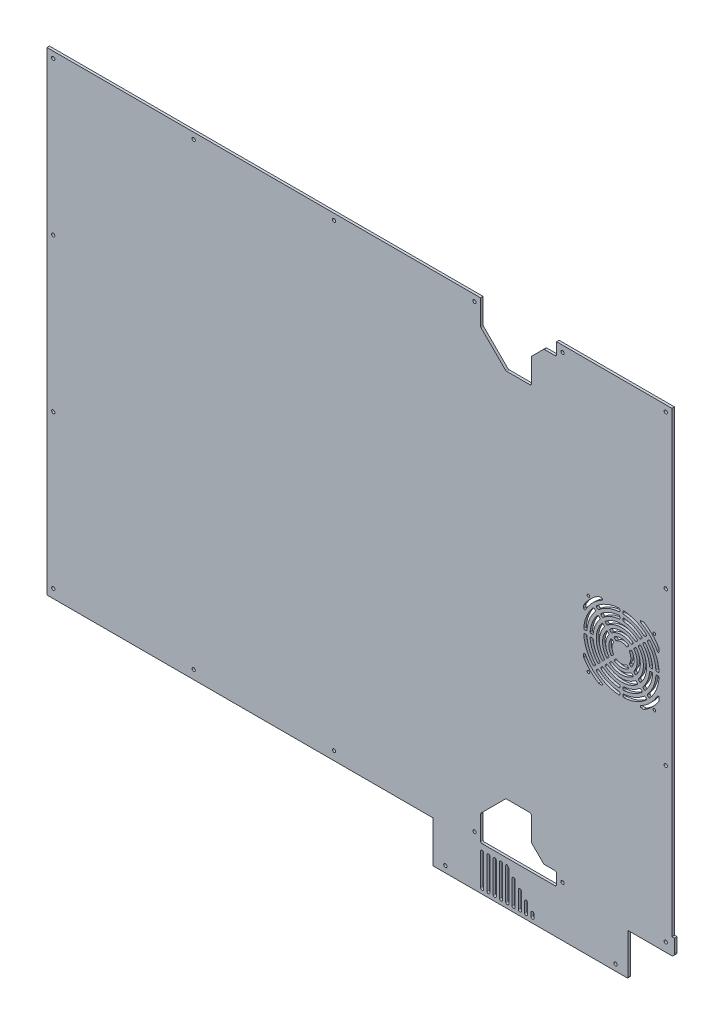
SolidWorks part; units mm, degrees
material "PC Высокая вязкость"
ref_plane "Спереди" through (0, 0, 0) normal (0, 0, 1) x (1, 0, 0)
ref_plane "Сверху" through (0, 0, 0) normal (0, 1, 0) x (1, 0, 0)
ref_plane "Справа" through (0, 0, 0) normal (1, 0, 0) x (0, 0, -1)
sketch "Эскиз1" plane through (0, 0, 0) normal (0, 0, 1) x (1, 0, 0)
  line L68 (0, -4) -> (0, 750)
  line L81 (0, 375) -> (994, 375) construction
  line L82 (0, 0) -> (994, 0) construction
  line L83 (0, 0) -> (0, 750) construction
  line L84 (0, 750) -> (994, 750) construction
  line L85 (994, 0) -> (994, 750) construction
  line L86 (770, 0) -> (770, 750) construction
  line L95 (0, 750) -> (994, 750)
  line L96 (994, 750) -> (994, 22.45)
  line L97 (998, -4) -> (924, -4)
  line L114 (924, -4) -> (924, -70)
  line L115 (924, -70) -> (613.5, -70)
  line L116 (613.5, -70) -> (613.5, -4)
  line L117 (613.5, -4) -> (0, -4)
  line L127 (994, 22.45) -> (998, 22.45)
  line L130 (998, 22.45) -> (998, -4)
  dimension "D3" = 26.45
  dimension "D4" = 4
  dimension "D6" = 613.5
  dimension "D7" = 70
  dimension "D8" = 70
  dimension "D9" = 4
  dimension "D10" = 310.5
  dimension "D12" = 750
  dimension "D17" = 770
  dimension "D18" = 224
extrude "Бобышка-Вытянуть1" add sketch "Эскиз1" along normal blind 4
sketch "Эскиз7" plane through (0, 0, 4) normal (0, 0, 1) x (1, 0, 0)
  line L0 (690, 40) -> (730, 80) construction
  line L1 (730, 80) -> (770, 80) construction
  line L2 (770, 80) -> (770, 40) construction
  line L3 (770, 40) -> (790, 20) construction
  line L4 (790, 20) -> (810, 20) construction
  line L5 (810, 20) -> (810, 0) construction
  line L6 (690, 0) -> (810, 0) construction
  line L7 (690, 0) -> (690, 40) construction
  line L8 (0, 750) -> (0, -4) construction
  line L9 (770, 375) -> (-49230, 375) construction
  line L10 (689.6, -0.4) -> (810.4, -0.4)
  line L11 (810.4, 20.4) -> (810.4, -0.4)
  line L12 (790.1657, 20.4) -> (810.4, 20.4)
  line L13 (770.4, 40.1657) -> (790.1657, 20.4)
  line L14 (770.4, 80.4) -> (770.4, 40.1657)
  line L15 (729.8343, 80.4) -> (770.4, 80.4)
  line L16 (689.6, 40.1657) -> (729.8343, 80.4)
  line L17 (689.6, -0.4) -> (689.6, 40.1657)
  line L18 (0, 0) -> (998, 0) construction
  line L19 (998, -4) -> (998, 22.45) construction
  line L20 (924, -4) -> (998, -4) construction
  line L21 (770, 0) -> (770, 750) construction
  line L22 (994, 750) -> (0, 750) construction
  line L23 (689.6, 750.4) -> (689.6, 709.8343)
  line L24 (689.6, 750.4) -> (810.4, 750.4)
  line L25 (810.4, 729.6) -> (810.4, 750.4)
  line L26 (790.1657, 729.6) -> (810.4, 729.6)
  line L27 (770.4, 709.8343) -> (790.1657, 729.6)
  line L28 (770.4, 669.6) -> (770.4, 709.8343)
  line L29 (729.8343, 669.6) -> (770.4, 669.6)
  line L30 (689.6, 709.8343) -> (729.8343, 669.6)
  point P30 (770, 375)
  dimension "D1" = 40
  dimension "D2" = 120
  dimension "D3" = 40
  dimension "D4" = 20
  dimension "D5" = 40
  dimension "D6" = 20
  dimension "D7" = 40
  dimension "D8" = 40
  dimension "D9" = 20
  dimension "D10" = 20
  dimension "D11" = 770
  dimension "D12" = 4
  dimension "D13" = 0.4
extrude "Вырез-Вытянуть6" cut sketch "Эскиз7" against normal through all
sketch "Эскиз2" plane through (0, 0, 0) normal (0, 0, -1) x (-1, 0, 0)
  line L0 (-984, 739.99) -> (-820, 739.99) construction
  line L1 (-924, -4) -> (-998, -4) construction
  line L2 (-10, 10) -> (-10, 253.33) construction
  line L3 (-10, 10) -> (-233.33, 10) construction
  line L7 (-984, 10) -> (-984, 253.33) construction
  line L10 (-994, 22.45) -> (-994, 750) construction
  line L11 (0, 750) -> (0, -4) construction
  circle A0 centre (-10, 10) radius 2.6
  circle A1 centre (-10, 253.33) radius 2.6
  circle A2 centre (-10, 496.66) radius 2.6
  circle A3 centre (-10, 739.99) radius 2.6
  circle A16 centre (-984, 10) radius 2.6
  circle A17 centre (-984, 253.33) radius 2.6
  circle A18 centre (-984, 496.66) radius 2.6
  circle A19 centre (-984, 739.99) radius 2.6
  circle A261 centre (-820, 739.99) radius 2.6
  circle A262 centre (-820, 10) radius 2.6
  circle A263 centre (-233.33, 10) radius 2.6
  circle A264 centre (-233.33, 739.99) radius 2.6
  circle A265 centre (-456.66, 10) radius 2.6
  circle A266 centre (-456.66, 739.99) radius 2.6
  circle A267 centre (-679.99, 10) radius 2.6
  circle A268 centre (-679.99, 739.99) radius 2.6
  dimension "D1" = 5.2
  dimension "D10" = 5.2
  dimension "D11" = 14
  dimension "D12" = 10
  dimension "D2" = 4
  dimension "D3" = 10
  dimension "D5" = 243.33
  dimension "D9" = 164
  dimension "D14" = 243.33
  dimension "D6" = 223.33
  dimension "D4" = 4
  dimension "D13" = 4
  dimension "D8" = 2
extrude "Вырез-Вытянуть1" cut sketch "Эскиз2" against normal through all
sketch "Эскиз3" plane through (0, 0, 4) normal (0, 0, 1) x (1, 0, 0)
  line L0 (774.5, -62) -> (774.5, -12)
  line L2 (769.5, -12) -> (769.5, -62)
  line L4 (759.5, -12) -> (759.5, -62)
  line L5 (764.5, -62) -> (764.5, -12)
  line L6 (749.5, -12) -> (749.5, -62)
  line L7 (754.5, -62) -> (754.5, -12)
  line L12 (924, -70) -> (924, -4) construction
  line L13 (924, -37) -> (-49076, -37) construction
  line L14 (739.5, -12) -> (739.5, -62)
  line L15 (744.5, -62) -> (744.5, -12)
  line L16 (729.5, -12) -> (729.5, -62)
  line L17 (734.5, -62) -> (734.5, -12)
  line L18 (719.5, -12) -> (719.5, -62)
  line L19 (724.5, -62) -> (724.5, -12)
  line L20 (709.5, -12) -> (709.5, -62)
  line L21 (714.5, -62) -> (714.5, -12)
  line L22 (699.5, -12) -> (699.5, -62)
  line L23 (704.5, -62) -> (704.5, -12)
  line L24 (769.5, -12) -> (759.5, -12) construction
  line L25 (689.5, -12) -> (689.5, -62)
  line L26 (694.5, -62) -> (694.5, -12)
  arc A0 (774.5, -12) -> (769.5, -12) centre (772, -12) ccw
  arc A1 (774.5, -62) -> (769.5, -62) centre (772, -62) cw
  arc A2 (764.5, -62) -> (759.5, -62) centre (762, -62) cw
  arc A3 (764.5, -12) -> (759.5, -12) centre (762, -12) ccw
  arc A4 (754.5, -62) -> (749.5, -62) centre (752, -62) cw
  arc A5 (754.5, -12) -> (749.5, -12) centre (752, -12) ccw
  arc A6 (744.5, -62) -> (739.5, -62) centre (742, -62) cw
  arc A7 (744.5, -12) -> (739.5, -12) centre (742, -12) ccw
  arc A8 (734.5, -62) -> (729.5, -62) centre (732, -62) cw
  arc A9 (734.5, -12) -> (729.5, -12) centre (732, -12) ccw
  arc A10 (724.5, -62) -> (719.5, -62) centre (722, -62) cw
  arc A11 (724.5, -12) -> (719.5, -12) centre (722, -12) ccw
  arc A12 (714.5, -62) -> (709.5, -62) centre (712, -62) cw
  arc A13 (714.5, -12) -> (709.5, -12) centre (712, -12) ccw
  arc A14 (704.5, -62) -> (699.5, -62) centre (702, -62) cw
  arc A15 (704.5, -12) -> (699.5, -12) centre (702, -12) ccw
  arc A16 (694.5, -62) -> (689.5, -62) centre (692, -62) cw
  arc A17 (694.5, -12) -> (689.5, -12) centre (692, -12) ccw
  point P6 (774.5, -37)
  point P17 (924, -37)
  dimension "D4" = 50
  dimension "D2" = 149.5
  dimension "D3" = 5
  dimension "D5" = 10
  dimension "D1" = 9
extrude "Вырез-Вытянуть2" cut sketch "Эскиз3" against normal through all
sketch "Эскиз5" plane through (0, 0, 4) normal (0, 0, 1) x (1, 0, 0)
  line L0 (730, -8) -> (784.5, -8)
  line L1 (784.5, -8) -> (784.5, -66)
  line L2 (784.5, -66) -> (730, -8)
  line L5 (0, -4) -> (613.5, -4) construction
  line L6 (774.5, -62) -> (774.5, -12) construction
  dimension "D1" = 54.5
  dimension "D2" = 58
  dimension "D3" = 4
  dimension "D4" = 10
extrude "Бобышка-Вытянуть2" add sketch "Эскиз5" against normal up to surface (4 mm away) up to face at (692, -37, 0)
sketch "Эскиз4" plane through (0, 0, 4) normal (0, 0, 1) x (1, 0, 0)
  line L0 (924, -70) -> (924, -4) construction
  line L1 (613.5, -70) -> (924, -70) construction
  line L2 (613.5, -4) -> (613.5, -70) construction
  circle A0 centre (904, -60) radius 2.6
  circle A1 centre (633.5, -60) radius 2.6
  dimension "D1" = 5.2
  dimension "D2" = 20
  dimension "D4" = 20
  dimension "D3" = 10
  dimension "D5" = 10
extrude "Вырез-Вытянуть3" cut sketch "Эскиз4" against normal through all
fillet "Скругление1" radius 2.5 14 edges at (729.8343, 80.4, 2) (770.4, 80.4, 2) (770.4, 40.1657, 2) (790.1657, 20.4, 2) (810.4, 20.4, 2) (810.4, -0.4, 2) (689.6, 40.1657, 2) (689.6, -0.4, 2) (810.4, 729.6, 2) (790.1657, 729.6, 2) (770.4, 709.8343, 2) (770.4, 669.6, 2) (729.8343, 669.6, 2) (689.6, 709.8343, 2)
fillet "Скругление2" radius 1.5 2 edges at (613.5, -70, 2) (924, -70, 2)
fillet "Скругление3" radius 5.5 1 edges at (998, -4, 2)
fillet "Скругление4" radius 2.5 8 edges at (764.5, -44.7156, 2) (759.5, -39.3945, 2) (754.5, -34.0734, 2) (749.5, -28.7523, 2) (739.5, -18.1101, 2) (744.5, -23.4312, 2) (769.5, -50.0367, 2) (774.5, -55.3578, 2)
sketch "Эскиз6" plane through (0, 0, 4) normal (0, 0, 1) x (1, 0, 0)
  line L0 (973.5, 433) -> (853.5, 313) construction
  line L1 (973.5, 433) -> (853.5, 433) construction
  line L2 (973.5, 433) -> (973.5, 313) construction
  line L3 (973.5, 313) -> (853.5, 313) construction
  line L4 (853.5, 433) -> (853.5, 313) construction
  line L5 (853.5, 433) -> (973.5, 313) construction
  line L6 (901.274, 381.6905) -> (897.701, 385.2634)
  line L20 (901.274, 364.3095) -> (897.701, 360.7366)
  line L21 (894.1432, 388.8213) -> (890.5928, 392.3717)
  line L22 (894.1432, 357.1787) -> (890.5928, 353.6283)
  line L23 (887.0467, 395.9178) -> (883.5033, 399.4612)
  line L24 (887.0467, 350.0822) -> (883.5033, 346.5388)
  line L29 (913.5, 373) -> (853.267, 373) construction
  line L30 (879.9616, 403.0029) -> (876.4211, 406.5434)
  line L31 (879.9616, 342.9971) -> (876.4211, 339.4566)
  line L32 (872.8816, 410.0829) -> (869.3427, 413.6218)
  line L33 (872.8816, 335.9171) -> (869.3427, 332.3782)
  line L34 (853.5, 409.0555) -> (853.5, 398)
  line L35 (853.5, 348) -> (853.5, 336.9445)
  line L36 (853.5521, 375.5) -> (858.5568, 375.5)
  line L37 (853.5521, 370.5) -> (858.5568, 370.5)
  line L38 (863.5625, 375.5) -> (868.5695, 375.5)
  line L39 (863.5625, 370.5) -> (868.5695, 370.5)
  line L40 (904.8095, 385.226) -> (901.2366, 388.799)
  line L41 (922.1905, 385.226) -> (925.7634, 388.799)
  line L42 (929.3213, 392.3568) -> (932.8717, 395.9072)
  line L43 (897.6787, 392.3568) -> (894.1283, 395.9072)
  line L44 (936.4178, 399.4533) -> (939.9612, 402.9967)
  line L45 (890.5822, 399.4533) -> (887.0388, 402.9967)
  line L46 (916, 422.9375) -> (916, 417.9305)
  line L47 (943.5029, 406.5384) -> (947.0434, 410.0789)
  line L48 (950.5829, 413.6184) -> (954.1218, 417.1573)
  line L49 (916, 432.9479) -> (916, 427.9432)
  line L50 (883.4971, 406.5384) -> (879.9566, 410.0789)
  line L51 (911, 422.9375) -> (911, 417.9305)
  line L52 (876.4171, 413.6184) -> (872.8782, 417.1573)
  line L53 (911, 432.9479) -> (911, 427.9432)
  line L54 (949.5555, 433) -> (938.5, 433)
  line L55 (888.5, 433) -> (877.4445, 433)
  line L56 (925.726, 381.6905) -> (929.299, 385.2634)
  line L57 (925.726, 364.3095) -> (929.299, 360.7366)
  line L58 (932.8568, 357.1787) -> (936.4072, 353.6283)
  line L59 (932.8568, 388.8213) -> (936.4072, 392.3717)
  line L60 (939.9533, 350.0822) -> (943.4967, 346.5388)
  line L61 (939.9533, 395.9178) -> (943.4967, 399.4612)
  line L62 (963.4375, 370.5) -> (958.4305, 370.5)
  line L63 (947.0384, 342.9971) -> (950.5789, 339.4566)
  line L64 (954.1184, 335.9171) -> (957.6573, 332.3782)
  line L65 (973.4479, 370.5) -> (968.4432, 370.5)
  line L66 (947.0384, 403.0029) -> (950.5789, 406.5434)
  line L67 (963.4375, 375.5) -> (958.4305, 375.5)
  line L68 (954.1184, 410.0829) -> (957.6573, 413.6218)
  line L69 (973.4479, 375.5) -> (968.4432, 375.5)
  line L70 (973.5, 336.9445) -> (973.5, 348)
  line L71 (973.5, 398) -> (973.5, 409.0555)
  line L72 (922.1905, 360.774) -> (925.7634, 357.201)
  line L73 (904.8095, 360.774) -> (901.2366, 357.201)
  line L74 (897.6787, 353.6432) -> (894.1283, 350.0928)
  line L75 (929.3213, 353.6432) -> (932.8717, 350.0928)
  line L76 (890.5822, 346.5467) -> (887.0388, 343.0033)
  line L77 (936.4178, 346.5467) -> (939.9612, 343.0033)
  line L78 (911, 323.0625) -> (911, 328.0695)
  line L79 (883.4971, 339.4616) -> (879.9566, 335.9211)
  line L80 (876.4171, 332.3816) -> (872.8782, 328.8427)
  line L81 (911, 313.0521) -> (911, 318.0568)
  line L82 (943.5029, 339.4616) -> (947.0434, 335.9211)
  line L83 (916, 323.0625) -> (916, 328.0695)
  line L84 (950.5829, 332.3816) -> (954.1218, 328.8427)
  line L85 (916, 313.0521) -> (916, 318.0568)
  line L86 (877.4445, 313) -> (888.5, 313)
  line L87 (938.5, 313) -> (949.5555, 313)
  line L88 (994, 22.45) -> (994, 750) construction
  line L89 (0, 373) -> (50000, 373) construction
  line L90 (0, 750) -> (0, -4) construction
  arc A0 (901.274, 381.6905) -> (901.274, 364.3095) centre (913.5, 373) ccw
  arc A1 (897.701, 385.2634) -> (897.701, 360.7366) centre (913.5, 373) ccw
  arc A2 (894.1432, 388.8213) -> (894.1432, 357.1787) centre (913.5, 373) ccw
  arc A3 (890.5928, 392.3717) -> (890.5928, 353.6283) centre (913.5, 373) ccw
  arc A4 (887.0467, 395.9178) -> (887.0467, 350.0822) centre (913.5, 373) ccw
  arc A5 (883.5033, 399.4612) -> (883.5033, 346.5388) centre (913.5, 373) ccw
  arc A6 (879.9616, 403.0029) -> (868.5695, 375.5) centre (913.5, 373) ccw
  arc A7 (876.4211, 406.5434) -> (863.5625, 375.5) centre (913.5, 373) ccw
  arc A9 (872.8816, 410.0829) -> (858.5568, 375.5) centre (913.5, 373) ccw
  arc A10 (869.3427, 413.6218) -> (853.5521, 375.5) centre (913.5, 373) ccw
  arc A11 (867.5381, 418.9619) -> (853.5, 398) centre (913.5, 373) ccw
  arc A12 (864.0025, 422.4975) -> (853.5, 409.0555) centre (913.5, 373) ccw
  arc A13 (853.5, 336.9445) -> (864.0025, 323.5025) centre (913.5, 373) ccw
  arc A14 (853.5, 348) -> (867.5381, 327.0381) centre (913.5, 373) ccw
  arc A15 (868.5695, 370.5) -> (879.9616, 342.9971) centre (913.5, 373) ccw
  arc A16 (863.5625, 370.5) -> (876.4211, 339.4566) centre (913.5, 373) ccw
  arc A17 (858.5568, 370.5) -> (872.8816, 335.9171) centre (913.5, 373) ccw
  arc A18 (853.5521, 370.5) -> (869.3427, 332.3782) centre (913.5, 373) ccw
  circle A20 centre (861, 425.5) radius 2.1
  arc A21 (925.7634, 388.799) -> (901.2366, 388.799) centre (913.5, 373) ccw
  arc A22 (922.1905, 385.226) -> (904.8095, 385.226) centre (913.5, 373) ccw
  arc A23 (932.8717, 395.9072) -> (894.1283, 395.9072) centre (913.5, 373) ccw
  arc A24 (929.3213, 392.3568) -> (897.6787, 392.3568) centre (913.5, 373) ccw
  arc A25 (939.9612, 402.9967) -> (887.0388, 402.9967) centre (913.5, 373) ccw
  arc A26 (936.4178, 399.4533) -> (890.5822, 399.4533) centre (913.5, 373) ccw
  arc A27 (943.5029, 406.5384) -> (916, 417.9305) centre (913.5, 373) ccw
  arc A28 (947.0434, 410.0789) -> (916, 422.9375) centre (913.5, 373) ccw
  arc A29 (954.1218, 417.1573) -> (916, 432.9479) centre (913.5, 373) ccw
  arc A30 (950.5829, 413.6184) -> (916, 427.9432) centre (913.5, 373) ccw
  arc A31 (911, 417.9305) -> (883.4971, 406.5384) centre (913.5, 373) ccw
  arc A32 (911, 422.9375) -> (879.9566, 410.0789) centre (913.5, 373) ccw
  arc A33 (911, 432.9479) -> (872.8782, 417.1573) centre (913.5, 373) ccw
  arc A34 (911, 427.9432) -> (876.4171, 413.6184) centre (913.5, 373) ccw
  circle A35 centre (966, 425.5) radius 2.1
  arc A36 (962.9975, 422.4975) -> (949.5555, 433) centre (913.5, 373) ccw
  arc A37 (959.4619, 418.9619) -> (938.5, 433) centre (913.5, 373) ccw
  arc A38 (877.4445, 433) -> (864.0025, 422.4975) centre (913.5, 373) ccw
  arc A39 (888.5, 433) -> (867.5381, 418.9619) centre (913.5, 373) ccw
  arc A40 (929.299, 360.7366) -> (929.299, 385.2634) centre (913.5, 373) ccw
  arc A41 (925.726, 364.3095) -> (925.726, 381.6905) centre (913.5, 373) ccw
  arc A42 (936.4072, 353.6283) -> (936.4072, 392.3717) centre (913.5, 373) ccw
  arc A43 (932.8568, 357.1787) -> (932.8568, 388.8213) centre (913.5, 373) ccw
  arc A44 (943.4967, 346.5388) -> (943.4967, 399.4612) centre (913.5, 373) ccw
  arc A45 (939.9533, 350.0822) -> (939.9533, 395.9178) centre (913.5, 373) ccw
  arc A46 (947.0384, 342.9971) -> (958.4305, 370.5) centre (913.5, 373) ccw
  arc A47 (950.5789, 339.4566) -> (963.4375, 370.5) centre (913.5, 373) ccw
  arc A48 (957.6573, 332.3782) -> (973.4479, 370.5) centre (913.5, 373) ccw
  arc A49 (954.1184, 335.9171) -> (968.4432, 370.5) centre (913.5, 373) ccw
  arc A50 (958.4305, 375.5) -> (947.0384, 403.0029) centre (913.5, 373) ccw
  arc A51 (963.4375, 375.5) -> (950.5789, 406.5434) centre (913.5, 373) ccw
  arc A52 (973.4479, 375.5) -> (957.6573, 413.6218) centre (913.5, 373) ccw
  arc A53 (968.4432, 375.5) -> (954.1184, 410.0829) centre (913.5, 373) ccw
  circle A54 centre (966, 320.5) radius 2.1
  arc A55 (962.9975, 323.5025) -> (973.5, 336.9445) centre (913.5, 373) ccw
  arc A56 (959.4619, 327.0381) -> (973.5, 348) centre (913.5, 373) ccw
  arc A57 (973.5, 409.0555) -> (962.9975, 422.4975) centre (913.5, 373) ccw
  arc A58 (973.5, 398) -> (959.4619, 418.9619) centre (913.5, 373) ccw
  arc A59 (901.2366, 357.201) -> (925.7634, 357.201) centre (913.5, 373) ccw
  arc A60 (904.8095, 360.774) -> (922.1905, 360.774) centre (913.5, 373) ccw
  arc A61 (894.1283, 350.0928) -> (932.8717, 350.0928) centre (913.5, 373) ccw
  arc A62 (897.6787, 353.6432) -> (929.3213, 353.6432) centre (913.5, 373) ccw
  arc A63 (887.0388, 343.0033) -> (939.9612, 343.0033) centre (913.5, 373) ccw
  arc A64 (890.5822, 346.5467) -> (936.4178, 346.5467) centre (913.5, 373) ccw
  arc A65 (883.4971, 339.4616) -> (911, 328.0695) centre (913.5, 373) ccw
  arc A66 (879.9566, 335.9211) -> (911, 323.0625) centre (913.5, 373) ccw
  arc A67 (872.8782, 328.8427) -> (911, 313.0521) centre (913.5, 373) ccw
  arc A68 (876.4171, 332.3816) -> (911, 318.0568) centre (913.5, 373) ccw
  arc A69 (916, 328.0695) -> (943.5029, 339.4616) centre (913.5, 373) ccw
  arc A70 (916, 323.0625) -> (947.0434, 335.9211) centre (913.5, 373) ccw
  arc A71 (916, 313.0521) -> (954.1218, 328.8427) centre (913.5, 373) ccw
  arc A72 (916, 318.0568) -> (950.5829, 332.3816) centre (913.5, 373) ccw
  circle A73 centre (861, 320.5) radius 2.1
  arc A74 (864.0025, 323.5025) -> (877.4445, 313) centre (913.5, 373) ccw
  arc A75 (867.5381, 327.0381) -> (888.5, 313) centre (913.5, 373) ccw
  arc A76 (949.5555, 313) -> (962.9975, 323.5025) centre (913.5, 373) ccw
  arc A77 (938.5, 313) -> (959.4619, 327.0381) centre (913.5, 373) ccw
  point P126 (0, 373)
  point P161 (913.5, 373)
  dimension "D2" = 15
  dimension "D3" = 5
  dimension "D4" = 5
  dimension "D5" = 5
  dimension "D6" = 5
  dimension "D7" = 5
  dimension "D8" = 5
  dimension "D9" = 5
  dimension "D10" = 5
  dimension "D11" = 5
  dimension "D12" = 5
  dimension "D13" = 2.5
  dimension "D14" = 2.5
  dimension "D15" = 5
  dimension "D18" = 4.2
  dimension "D1" = 120
  dimension "D16" = 2.5
  dimension "D17" = 2.5
  dimension "D19" = 52.5
  dimension "D21" = 20.5
  dimension "D20" = 4
extrude "Вырез-Вытянуть5" cut sketch "Эскиз6" against normal through all
fillet "Скругление5" radius 1.5 128 edges at (890.5928, 392.3717, 2) (894.1432, 388.8213, 2) (894.1432, 357.1787, 2) (890.5928, 353.6283, 2) (943.5029, 339.4616, 2) (947.0434, 335.9211, 2) (916, 323.0625, 2) (916, 328.0695, 2) (879.9566, 335.9211, 2) (883.4971, 339.4616, 2) (911, 328.0695, 2) (911, 323.0625, 2) (954.1218, 417.1573, 2) (950.5829, 413.6184, 2) (916, 427.9432, 2) (916, 432.9479, 2) (890.5822, 399.4533, 2) (887.0388, 402.9967, 2) (939.9612, 402.9967, 2) (936.4178, 399.4533, 2) (932.8717, 395.9072, 2) (929.3213, 392.3568, 2) (897.6787, 392.3568, 2) (894.1283, 395.9072, 2) (947.0434, 410.0789, 2) (943.5029, 406.5384, 2) (916, 417.9305, 2) (916, 422.9375, 2) (925.7634, 388.799, 2) (922.1905, 385.226, 2) (904.8095, 385.226, 2) (901.2366, 388.799, 2) (973.5, 409.0555, 2) (973.5, 398, 2) (938.5, 433, 2) (949.5555, 433, 2) (911, 432.9479, 2) (911, 427.9432, 2) (876.4171, 413.6184, 2) (872.8782, 417.1573, 2) (853.5521, 370.5, 2) (858.5568, 370.5, 2) (869.3427, 332.3782, 2) (869.3427, 413.6218, 2) (872.8816, 410.0829, 2) (858.5568, 375.5, 2) (853.5521, 375.5, 2) (887.0467, 350.0822, 2) (883.5033, 346.5388, 2) (883.5033, 399.4612, 2) (887.0467, 395.9178, 2) (853.5, 336.9445, 2) (853.5, 348, 2) (888.5, 313, 2) (877.4445, 313, 2) (879.9616, 342.9971, 2) (876.4211, 339.4566, 2) (863.5625, 370.5, 2) (868.5695, 370.5, 2) (876.4211, 406.5434, 2) (879.9616, 403.0029, 2) (868.5695, 375.5, 2) (863.5625, 375.5, 2) (897.701, 385.2634, 2) (901.274, 381.6905, 2) (901.274, 364.3095, 2) (897.701, 360.7366, 2) (877.4445, 433, 2) (888.5, 433, 2) (853.5, 398, 2) (853.5, 409.0555, 2) (894.1283, 350.0928, 2) (897.6787, 353.6432, 2) (929.3213, 353.6432, 2) (932.8717, 350.0928, 2) (947.0384, 403.0029, 2) (950.5789, 406.5434, 2) (963.4375, 375.5, 2) (958.4305, 375.5, 2) (950.5789, 339.4566, 2) (947.0384, 342.9971, 2) (958.4305, 370.5, 2) (963.4375, 370.5, 2) (901.2366, 357.201, 2) (904.8095, 360.774, 2) (922.1905, 360.774, 2) (925.7634, 357.201, 2) (916, 313.0521, 2) (916, 318.0568, 2) (950.5829, 332.3816, 2) (954.1218, 328.8427, 2) (872.8782, 328.8427, 2) (876.4171, 332.3816, 2) (911, 318.0568, 2) (911, 313.0521, 2) (936.4178, 346.5467, 2) (939.9612, 343.0033, 2) (887.0388, 343.0033, 2) (890.5822, 346.5467, 2) (883.4971, 406.5384, 2) (879.9566, 410.0789, 2) (911, 422.9375, 2) (911, 417.9305, 2) (939.9533, 395.9178, 2) (943.4967, 399.4612, 2) (943.4967, 346.5388, 2) (939.9533, 350.0822, 2) (936.4072, 353.6283, 2) (932.8568, 357.1787, 2) (932.8568, 388.8213, 2) (936.4072, 392.3717, 2) (929.299, 360.7366, 2) (925.726, 364.3095, 2) (925.726, 381.6905, 2) (929.299, 385.2634, 2) (949.5555, 313, 2) (938.5, 313, 2) (973.5, 348, 2) (973.5, 336.9445, 2) (973.4479, 375.5, 2) (968.4432, 375.5, 2) (954.1184, 410.0829, 2) (957.6573, 413.6218, 2) (957.6573, 332.3782, 2) (954.1184, 335.9171, 2) (968.4432, 370.5, 2) (973.4479, 370.5, 2) (872.8816, 335.9171, 2)
